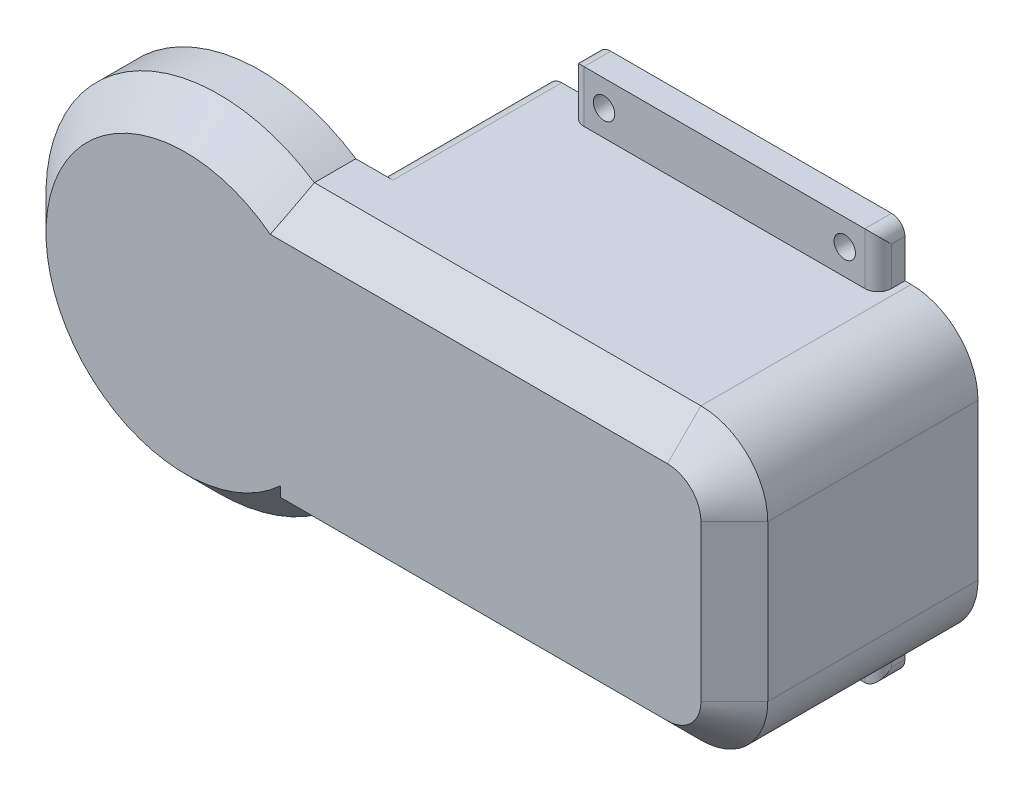
SolidWorks part; units mm, degrees
ref_plane "Alzado" through (0, 0, 0) normal (0, 0, 1) x (1, 0, 0)
ref_plane "Planta" through (0, 0, 0) normal (0, 1, 0) x (1, 0, 0)
ref_plane "Vista lateral" through (0, 0, 0) normal (1, 0, 0) x (0, 0, -1)
sketch "Croquis1" plane through (0, 0, 0) normal (0, 0, 1) x (1, 0, 0)
  line L1 (27.435, 10.11) -> (-27.435, 10.11) construction
  line L2 (27.435, 10.11) -> (27.435, -10.11) construction
  line L3 (27.435, -10.11) -> (-27.435, -10.11) construction
  line L4 (-27.435, 10.11) -> (-27.435, -10.11) construction
  line L5 (27.435, 10.11) -> (-27.435, -10.11) construction
  line L6 (27.435, -10.11) -> (-27.435, 10.11) construction
  line L7 (-33.935, 21.655) -> (33.935, 21.655)
  line L8 (33.935, 21.655) -> (33.935, -21.655)
  line L9 (33.935, -21.655) -> (-33.935, -21.655)
  line L12 (-27.435, -10.11) -> (27.435, -10.11)
  line L13 (27.435, -10.11) -> (27.435, 10.11)
  line L16 (-33.935, 15.155) -> (27.435, 15.155)
  line L17 (27.435, 15.155) -> (27.435, -15.155)
  line L18 (27.435, -15.155) -> (-33.935, -15.155)
  line L19 (-33.935, 21.655) -> (-33.935, 15.155)
  line L20 (-33.935, -15.155) -> (-33.935, -21.655)
  point P0 (0, 0)
  point P13 (33.935, 0)
  dimension "D1" = 54.87
  dimension "D2" = 20.22
  dimension "D3" = 43.31
  dimension "D4" = 6.5
  dimension "D5" = 6.5
  dimension "D6" = 6.5
extrude "Saliente-Extruir1" add sketch "Croquis1" along normal blind 29.95 contours L18 L20 L9 L8 L7 L19 L16 L17 L13 region at (0, 20.8499, 0)
sketch "Croquis2" plane through (0, 0, 29.95) normal (0, 0, 1) x (1, 0, 0)
  line L1 (-33.935, 21.655) -> (33.935, 21.655) construction
  line L2 (-33.935, 21.655) -> (33.935, 21.655)
  line L3 (-33.935, 21.655) -> (-33.935, -21.655)
  line L4 (-33.935, -21.655) -> (33.935, -21.655)
  line L5 (33.935, 21.655) -> (33.935, -21.655)
  line L6 (-33.935, 21.655) -> (-33.935, 15.155) construction
extrude "Saliente-Extruir2" add sketch "Croquis2" along normal blind 6.5
sketch "Croquis3" plane through (0, 0, 29.95) normal (0, 0, -1) x (-1, 0, 0)
  line L0 (27.435, 10.11) -> (27.435, -10.11) construction
  line L2 (-27.435, 10.11) -> (27.435, 10.11) construction
  circle A0 centre (16.135, 0.11) radius 2.575
  dimension "D1" = 5.15
  dimension "D2" = 11.3
  dimension "D3" = 10
extrude "Saliente-Extruir3" add sketch "Croquis3" along normal blind 6.7
fillet "Redondeo3" radius 10 2 edges at (33.935, -21.655, 18.225) (33.935, 21.655, 18.225)
sketch "Croquis4" plane through (0, 0, 0) normal (0, 0, -1) x (-1, 0, 0)
  line L0 (33.935, 21.655) -> (-23.935, 21.655) construction
  line L4 (23, 29.405) -> (23, 21.655)
  line L5 (0, 0) -> (0, 21.655) construction
  line L7 (-23, 29.405) -> (-23, 21.655)
  line L10 (0, 0) -> (-27.435, 0) construction
  line L11 (-27.435, 15.155) -> (-27.435, -15.155) construction
  line L13 (23, -29.405) -> (23, -21.655)
  line L18 (-23, -29.405) -> (-23, -21.655)
  line L19 (-23, -21.655) -> (23, -21.655)
  line L20 (23, -29.405) -> (-23, -29.405)
  line L21 (-23, 29.405) -> (23, 29.405)
  line L22 (-23, 21.655) -> (23, 21.655)
  dimension "D1" = 7.75
  dimension "D2" = 46
extrude "Saliente-Extruir4" add sketch "Croquis4" against normal blind 4
chamfer "Chaflán2" distance 3.5 angle 45 2 edges at (-3.25, -15.155, 0) (-3.25, 15.155, 0)
chamfer "Chaflán1" distance 5 angle 45 5 edges at (-5, -21.655, 36.45) (-5, 21.655, 36.45) (31.0061, -18.7261, 36.45) (33.935, 0, 36.45) (31.0061, 18.7261, 36.45)
sketch "Croquis5" plane through (0, 0, 29.95) normal (0, 0, -1) x (-1, 0, 0)
  circle A0 centre (16.135, 0.11) radius 12.76 construction
  circle A1 centre (48.18, 0.11) radius 22.285 construction
  circle A2 centre (48.18, 0.11) radius 20.785 construction
  circle A3 centre (16.135, 0.11) radius 11.26 construction
  circle A4 centre (48.18, 0.11) radius 25.855
  dimension "D1" = 25.52
  dimension "D2" = 44.57
  dimension "D3" = 41.57
  dimension "D4" = 22.52
  dimension "D5" = 3.57
extrude "Cortar-Extruir1" cut sketch "Croquis5" along normal up to surface (29.95 mm away) up to face at (2.1673, 0, 0)
sketch "Croquis6" plane through (0, 0, 36.45) normal (0, 0, 1) x (1, 0, 0)
  circle A0 centre (-48.18, 0.11) radius 25.855 construction
  circle A1 centre (-48.18, 0.11) radius 25.855
extrude "Saliente-Extruir5" add sketch "Croquis6" against normal up to surface (6.5 mm away) up to face at (-14.3963, 3.1222, 29.95)
sketch "Croquis7" plane through (0, 0, 29.95) normal (0, 0, -1) x (-1, 0, 0)
  circle A0 centre (48.18, 0.11) radius 2.575
  dimension "D1" = 5.15
extrude "Saliente-Extruir6" add sketch "Croquis7" along normal blind 6.7
sketch "Croquis8" plane through (0, 0, 29.95) normal (0, 0, -1) x (-1, 0, 0)
  line L0 (27.1531, 15.155) -> (27.3123, -15.155) construction
  line L1 (27.1531, 15.155) -> (30.3165, 15.155)
  line L2 (27.3123, -15.155) -> (30.5041, -15.155)
  circle A0 centre (48.18, 0.11) radius 25.855 construction
  arc A1 (27.3123, -15.155) -> (27.1531, 15.155) centre (48.18, 0.11) ccw
  arc A2 (30.5041, -15.155) -> (30.3165, 15.155) centre (48.18, 0.11) ccw
  circle A3 centre (48.18, 0.11) radius 25.855 construction
  circle A4 centre (48.18, 0.11) radius 23.355 construction
  dimension "D1" = 2.5
extrude "Saliente-Extruir7" add sketch "Croquis8" along normal blind 4.7
chamfer "Chaflán3" distance 5 angle 45 1 edges at (-74.0346, 0.2538, 36.45)
sketch "Croquis9" plane through (0, 0, 4) normal (0, 0, 1) x (1, 0, 0)
  line L1 (-23, 21.655) -> (-23, 29.405) construction
  line L2 (0, 0) -> (0, 21.655) construction
  line L3 (-33.8869, 21.655) -> (23.935, 21.655) construction
  line L4 (0, 0) -> (33.935, 0) construction
  line L5 (33.935, 11.655) -> (33.935, -11.655) construction
  line L7 (-23, 21.655) -> (-23, 29.405) construction
  circle A0 centre (-18, 25.53) radius 1.6
  circle A1 centre (18, 25.53) radius 1.6
  circle A2 centre (18, -25.53) radius 1.6
  circle A3 centre (-18, -25.53) radius 1.6
  point P8 (-23, 25.53)
  dimension "D1" = 3.2
  dimension "D2" = 5
extrude "Cortar-Extruir2" cut sketch "Croquis9" against normal through all
fillet "Redondeo6" radius 2 8 edges at (-23, 25.53, 4) (-23, -25.53, 4) (23, -25.53, 4) (23, 25.53, 4) (-23, -29.405, 2) (23, -29.405, 2) (23, 29.405, 2) (-23, 29.405, 2)
fillet "Redondeo4" radius 2 2 edges at (-33.935, -21.655, 15.725) (-33.8869, 21.655, 12.625)
fillet "Redondeo5" radius 2 1 edges at (-33.3496, -21.0688, 12.625)
